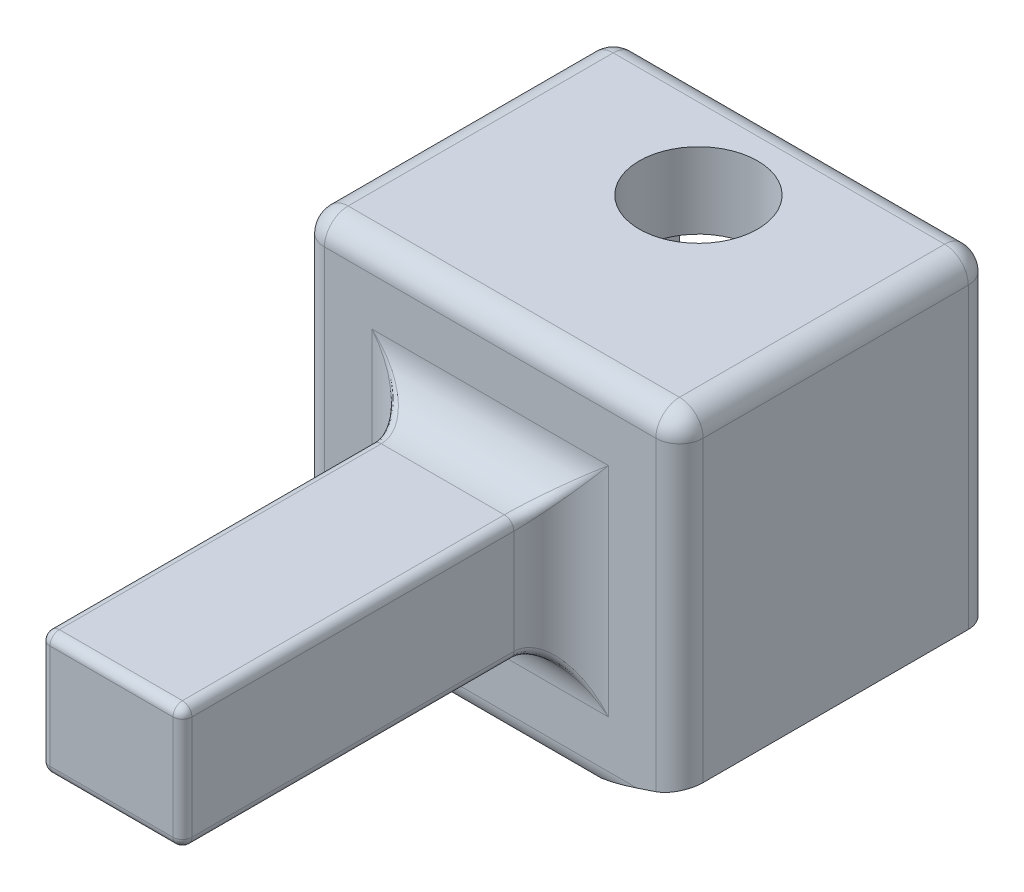
SolidWorks part; units mm, degrees
ref_plane "Front Plane" through (0, 0, 0) normal (0, 0, 1) x (1, 0, 0)
ref_plane "Top Plane" through (0, 0, 0) normal (0, 1, 0) x (1, 0, 0)
ref_plane "Right Plane" through (0, 0, 0) normal (1, 0, 0) x (0, 0, -1)
sketch "Sketch1" plane through (0, 0, 0) normal (0, 0, 1) x (1, 0, 0)
  line L0 (-4.318, -3.81) -> (4.318, -3.81)
  line L1 (-5.08, 4.826) -> (5.08, 4.826)
  line L2 (-5.08, 4.826) -> (-5.08, -4.826)
  line L3 (-5.08, -4.826) -> (5.08, -4.826)
  line L4 (5.08, 4.826) -> (5.08, -4.826)
  line L5 (-5.08, 4.826) -> (5.08, -4.826) construction
  line L6 (-5.08, -4.826) -> (5.08, 4.826) construction
  line L7 (4.318, -3.81) -> (4.318, -1.016)
  line L8 (4.318, -1.016) -> (3.302, -1.016)
  line L9 (3.302, -1.016) -> (3.302, 2.794)
  line L10 (3.302, 2.794) -> (-3.302, 2.794)
  line L11 (-3.302, 2.794) -> (-3.302, -1.016)
  line L12 (-3.302, -1.016) -> (-4.318, -1.016)
  line L13 (-4.318, -1.016) -> (-4.318, -3.81)
  point P5 (0, 2.794)
  point P7 (0, 0)
  dimension "D1" = 0.762
  dimension "D2" = 2.032
  dimension "D3" = 1.016
  dimension "D4" = 6.604
  dimension "D5" = 3.81
  dimension "D6" = 6.604
  dimension "D7" = 8.636
extrude "Boss-Extrude1" add sketch "Sketch1" along normal blind 7.112
sketch "Sketch2" plane through (0, 4.826, 0) normal (0, 1, 0) x (1, 0, 0)
  line L1 (5.08, 0) -> (-5.08, 0) construction
  circle A0 centre (0, -2.794) radius 1.5875
  dimension "D1" = 3.175
  dimension "D2" = 2.794
extrude "Cut-Extrude1" cut sketch "Sketch2" against normal through all both and the other way through all
sketch "Sketch3" plane through (0, 0, 7.112) normal (0, 0, 1) x (1, 0, 0)
  line L1 (-5.08, 4.826) -> (5.08, 4.826)
  line L2 (-5.08, 4.826) -> (-5.08, -4.826)
  line L3 (-5.08, -4.826) -> (5.08, -4.826)
  line L4 (5.08, 4.826) -> (5.08, -4.826)
sketch "Sketch7" plane through (0, 0, 7.112) normal (0, 0, 1) x (1, 0, 0)
  line L0 (-5.08, 4.826) -> (5.08, 4.826)
  line L1 (5.08, 4.826) -> (5.08, -4.826)
  line L2 (5.08, -4.826) -> (-5.08, -4.826)
  line L3 (-5.08, -4.826) -> (-5.08, 4.826)
extrude "Boss-Extrude3" add sketch "Sketch7" along normal blind 1.27
fillet "Fillet1" radius 0.635 3 edges at (-5.08, 0, 0) (0, 4.826, 0) (5.08, 0, 0)
fillet "Fillet3" radius 0.635 13 edges at (-5.08, 4.826, 4.5085) (5.08, 4.826, 4.5085) (-5.08, -4.826, 4.5085) (5.08, -4.826, 4.5085) (-4.894, 4.64, 0.186) (4.894, 4.64, 0.186) (-4.894, -4.826, 0.186) (0, -4.826, 0) (4.894, -4.826, 0.186) (0, 4.826, 8.382) (5.08, 0, 8.382) (0, -4.826, 8.382) (-5.08, 0, 8.382)
fillet "Fillet4" radius 0.381 2 edges at (-3.302, -1.016, 3.556) (3.302, -1.016, 3.556)
sketch "Sketch11" plane through (4.318, 0, 0) normal (-1, 0, 0) x (0, 0, 1)
  line L0 (0, -3.81) -> (5.08, -3.81)
  line L1 (5.08, -3.81) -> (5.08, -4.064)
  line L2 (0, -3.81) -> (0, -4.826)
  line L3 (0, -4.826) -> (10.16, -4.826)
  line L4 (7.747, -4.826) -> (0.635, -4.826) construction
  line L5 (10.16, -4.826) -> (5.08, -4.064)
  dimension "D1" = 0.254
  dimension "D2" = 5.08
  dimension "D3" = 10.16
extrude "Cut-Extrude3" cut sketch "Sketch11" against normal through all both and the other way through all
fillet "Fillet9" radius 0.254 3 edges at (0, -3.81, 7.112) (-4.318, -3.81, 6.096) (4.318, -3.81, 6.096)
sketch "Sketch13" plane through (0, 0, 5.08) normal (0, 0, -1) x (-1, 0, 0)
  line L0 (-5.08, -3.81) -> (-5.08, -4.826)
  line L1 (-5.08, -4.826) -> (-2.032, -4.826)
  line L2 (5.08, -4.826) -> (-5.08, -4.826) construction
  line L3 (-4.318, -3.81) -> (-4.318, -4.064) construction
  line L4 (-5.08, -4.064) -> (5.08, -4.064) construction
  line L5 (-5.08, -3.81) -> (-2.032, -4.826)
  line L6 (5.08, -3.81) -> (5.08, -4.826)
  line L7 (5.08, -4.826) -> (2.032, -4.826)
  line L8 (4.318, -3.81) -> (4.318, -4.064) construction
  line L9 (5.08, -3.81) -> (2.032, -4.826)
extrude "Cut-Extrude7" cut sketch "Sketch13" against normal through all
sketch "Sketch14" plane through (0, 0, 8.382) normal (0, 0, 1) x (1, 0, 0)
  line L8 (-1.905, 1.651) -> (-1.905, -1.651)
  line L9 (-1.905, 1.651) -> (-1.905, -1.651)
  line L10 (-1.905, -1.651) -> (1.905, -1.651)
  line L11 (-1.905, -1.651) -> (1.905, -1.651)
  line L12 (1.905, -1.651) -> (1.905, 1.651)
  line L13 (1.905, -1.651) -> (1.905, 1.651)
  line L14 (1.905, 1.651) -> (-1.905, 1.651)
  line L15 (1.905, 1.651) -> (-1.905, 1.651)
  dimension "D1" = 2.54
extrude "Boss-Extrude4" add sketch "Sketch14" along normal blind 10.16
fillet "Fillet14" radius 1.27 4 edges at (-1.905, 0, 8.382) (0, -1.651, 8.382) (1.905, 0, 8.382) (0, 1.651, 8.382)
fillet "Fillet15" radius 0.254 12 edges at (2.277, -2.023, 8.754) (-2.277, -2.023, 8.754) (-2.277, 2.023, 8.754) (2.277, 2.023, 8.754) (1.905, 0, 18.542) (1.905, -1.651, 14.097) (-1.905, 0, 18.542) (0, -1.651, 18.542) (0, 1.651, 18.542) (-1.905, -1.651, 14.097) (-1.905, 1.651, 14.097) (1.905, 1.651, 14.097)
